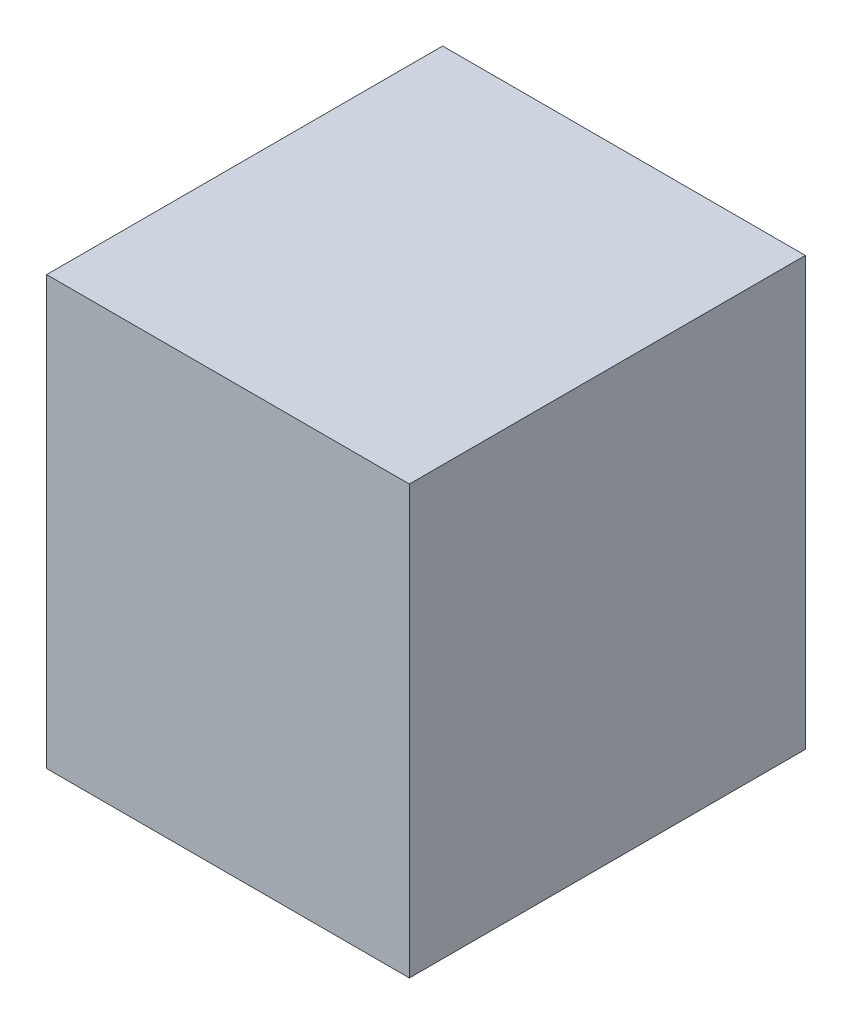
SolidWorks part; units mm, degrees
ref_plane "Front Plane" through (0, 0, 0) normal (0, 0, 1) x (1, 0, 0)
ref_plane "Top Plane" through (0, 0, 0) normal (0, 1, 0) x (1, 0, 0)
ref_plane "Right Plane" through (0, 0, 0) normal (1, 0, 0) x (0, 0, -1)
sketch "Sketch1" plane through (0, 0, 0) normal (0, 1, 0) x (1, 0, 0)
  line L1 (-36.5147, 51.1649) -> (48.2793, 51.1649)
  line L2 (-36.5147, 51.1649) -> (-36.5147, -41.3981)
  line L3 (-36.5147, -41.3981) -> (48.2793, -41.3981)
  line L4 (48.2793, 51.1649) -> (48.2793, -41.3981)
extrude "Boss-Extrude1" add sketch "Sketch1" along normal blind 100
